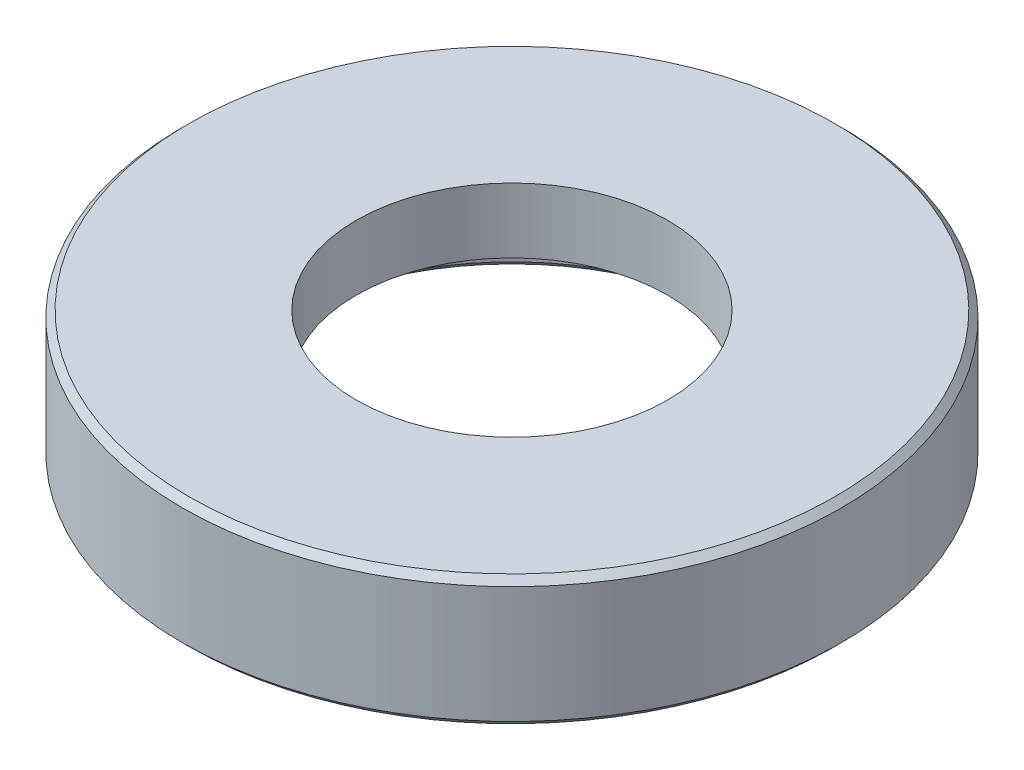
SolidWorks part; units mm, degrees
ref_plane "Front Plane" through (0, 0, 0) normal (0, 0, 1) x (1, 0, 0)
ref_plane "Top Plane" through (0, 0, 0) normal (0, 1, 0) x (1, 0, 0)
ref_plane "Right Plane" through (0, 0, 0) normal (1, 0, 0) x (0, 0, -1)
sketch "Sketch1" plane through (0, 0, 0) normal (0, 1, 0) x (1, 0, 0)
  circle A0 centre (0, 0) radius 6
  circle A1 centre (0, 0) radius 9
  circle A2 centre (0, 0) radius 12.7
extrude "Boss-Extrude1" add sketch "Sketch1" along normal blind 5 contours A2
extrude "Cut-Extrude1" cut sketch "Sketch1<3>" along normal up to surface (5 mm away) contours A0 up to face at (0, 5, 12.7)
sketch "Sketch1<3>" plane through (0, 0, 0) normal (0, 1, 0) x (1, 0, 0) same geometry as "Sketch1"
extrude "Cut-Extrude2" cut sketch "Sketch1<4>" along normal blind 2.5 contours A1 A0 region at (-8.7454, 0, 0)
sketch "Sketch1<4>" plane through (0, 0, 0) normal (0, 1, 0) x (1, 0, 0) same geometry as "Sketch1"
chamfer "Chamfer1" distance 0.25 angle 45 3 edges at (0, 5, 12.7) (0, 0, 9) (0, 0, 12.7)
